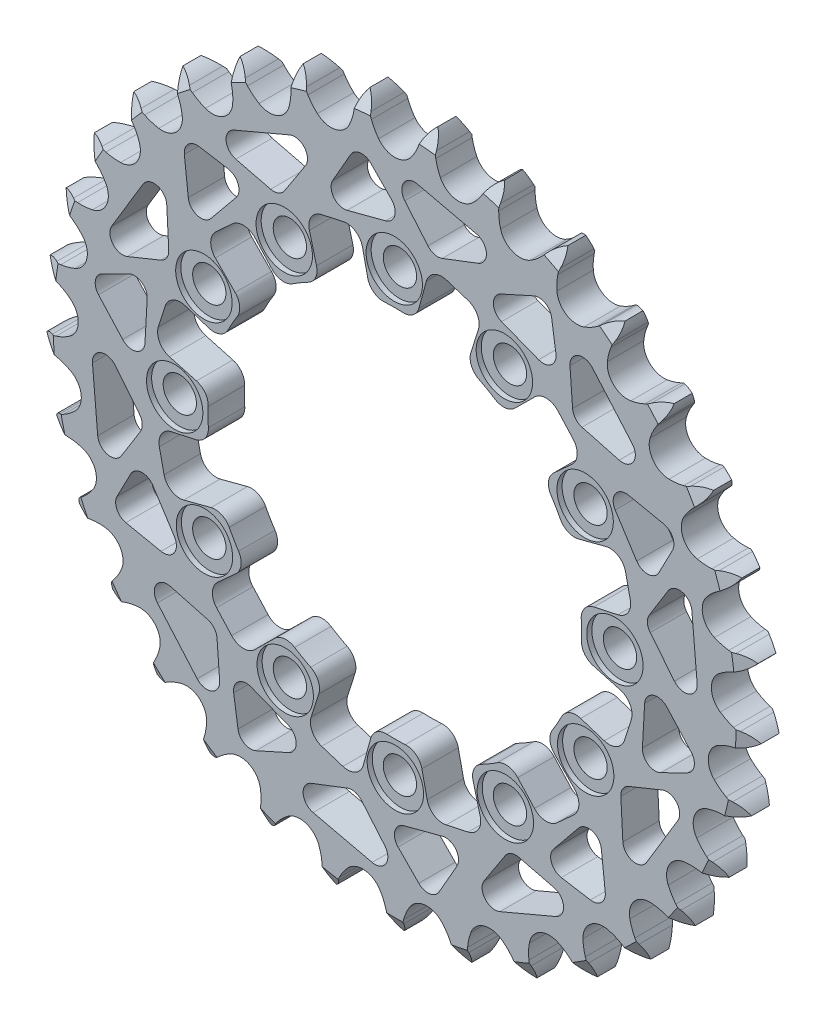
SolidWorks part; units mm, degrees
other "Markup1"
sketch "Sketch16" plane through (70.768, -70.8482, 7.2136) normal (0.1919, -0.04, 0.9806) x (0.9727, -0.1249, -0.1954)
sketch "Sketch17" plane through (70.768, -70.8482, 7.2136) normal (0.1919, -0.04, 0.9806) x (0.9727, -0.1249, -0.1954)
sketch "Sketch18" plane through (70.768, -70.8482, 7.2136) normal (0.1919, -0.04, 0.9806) x (0.9727, -0.1249, -0.1954)
sketch "Sketch19" plane through (70.768, -70.8482, 7.2136) normal (0.1919, -0.04, 0.9806) x (0.9727, -0.1249, -0.1954)
sketch "Sketch20" plane through (70.768, -70.8482, 7.2136) normal (0.1919, -0.04, 0.9806) x (0.9727, -0.1249, -0.1954)
sketch "Sketch24" plane through (70.768, -70.8482, 7.2136) normal (0.1919, -0.04, 0.9806) x (0.9727, -0.1249, -0.1954)
sketch "Sketch25" plane through (70.768, -70.8482, 7.2136) normal (0.1919, -0.04, 0.9806) x (0.9727, -0.1249, -0.1954)
sketch "Sketch26" plane through (70.768, -70.8482, 7.2136) normal (0.1919, -0.04, 0.9806) x (0.9727, -0.1249, -0.1954)
sketch "Sketch27" plane through (70.768, -70.8482, 7.2136) normal (0.1919, -0.04, 0.9806) x (0.9727, -0.1249, -0.1954)
sketch "Sketch28" plane through (70.768, -70.8482, 7.2136) normal (0.1919, -0.04, 0.9806) x (0.9727, -0.1249, -0.1954)
material "7075-T6 (SN)"
ref_plane "Front Plane" through (0, 0, 0) normal (0, 0, 1) x (1, 0, 0)
ref_plane "Top Plane" through (0, 0, 0) normal (0, 1, 0) x (1, 0, 0)
ref_plane "Right Plane" through (0, 0, 0) normal (1, 0, 0) x (0, 0, -1)
sketch "Work Sketch" plane through (0, 0, 0) normal (0, 0, 1) x (1, 0, 0)
  line L0 (0, 0) -> (0, 160.4542) construction
  line L1 (-112.0919, 66.8027) -> (87.2579, 66.8027) construction
  line L2 (5.0834, 120.8822) -> (5.0834, 112.9699) construction
  line L3 (-12.8497, 70.6081) -> (16.7256, 70.6081) construction
  line L4 (5.0834, 70.6081) -> (-6.0658, 62.2619) construction
  line L5 (5.0834, 70.6081) -> (-4.6352, 66.9715) construction
  line L6 (-4.6352, 66.9715) -> (-6.998, 73.2861)
  line L7 (-11.5114, 65.7464) -> (-7.1525, 65.7464) construction
  line L8 (-11.0622, 124.7602) -> (-11.0622, 110.2345) construction
  line L9 (0, 0) -> (-4.0639, 42.5596) construction
  circle A0 centre (0, 0) radius 66.8027
  circle A1 centre (0, 66.8027) radius 4.0088
  arc A2 (-4.6352, 66.9715) -> (-3.2092, 64.4003) centre (5.0609, 70.6677) ccw
  circle A3 centre (-11.0622, 65.7464) radius 6.4488
  point P23 (-3.2092, 64.4003)
  dimension "D1" = 133.6054
  dimension "D8" = 10.3767
  dimension "D2" = 8.0177
  dimension "D3" = 5.0834
  dimension "D4" = 3.8054
  dimension "D5" = 36.818
  dimension "D6" = 16.303
  dimension "D7" = 10.3767
  dimension "D9" = 1.0563
  dimension "D10" = 11.0622
  dimension "D11" = 5.455
sketch "Teeth Sketch" plane through (0, 0, 0) normal (0, 0, 1) x (1, 0, 0)
  line L0 (5.0224, 68.0064) -> (4.6352, 66.9715)
  line L1 (-8.8439, 92.6176) -> (-5.6513, 59.1829) construction
  line L2 (0, 0) -> (-12.8498, 132.1321) construction
  line L3 (7.9387, 67.7279) -> (8.123, 66.6385)
  line L4 (19011.2087, -199094.3845) -> (-19015.2726, 199136.9441) construction
  line L5 (0, 146.3285) -> (0, 56.9858) construction
  line L6 (17.8019, 65.8269) -> (17.2258, 64.8841)
  line L7 (0, -200000) -> (0, 200160.4542) construction
  line L8 (20.6128, 65.0016) -> (20.5877, 63.897)
  line L9 (-4.6352, 66.9715) -> (-6.998, 73.2861) construction
  line L10 (43.2949, 52.6844) -> (42.861, 51.6682)
  line L11 (-5.0224, 68.0064) -> (-4.6352, 66.9715)
  line L12 (29.938, 61.2683) -> (29.1939, 60.4515)
  line L13 (32.5419, 59.9259) -> (32.3082, 58.846)
  line L14 (40.9921, 54.4953) -> (40.1069, 53.8341)
  line L15 (50.5647, 45.7527) -> (49.5703, 45.271)
  line L16 (52.4831, 43.5387) -> (51.8648, 42.623)
  line L17 (58.3096, 35.3565) -> (57.2421, 35.0716)
  line L18 (59.7744, 32.8194) -> (58.9939, 32.0373)
  line L19 (63.9472, 23.6824) -> (62.845, 23.6047)
  line L20 (64.9053, 20.9139) -> (63.9909, 20.2936)
  line L21 (67.2735, 11.1523) -> (66.1765, 11.2846)
  line L22 (67.6904, 8.2526) -> (66.6751, 7.8165)
  line L23 (68.1683, -1.7808) -> (67.1162, -1.4433)
  line L24 (68.0289, -4.7071) -> (66.9495, -4.9431)
  line L25 (66.5994, -14.6496) -> (65.6302, -14.119)
  line L26 (65.9088, -17.4966) -> (64.8042, -17.524)
  line L27 (62.6234, -26.9889) -> (61.7722, -26.2845)
  line L28 (61.4065, -29.6537) -> (60.3166, -29.4716)
  line L29 (56.3841, -38.3527) -> (55.6815, -37.4999)
  line L30 (54.6848, -40.739) -> (53.6491, -40.354)
  line L31 (48.1068, -48.3304) -> (47.5783, -47.3601)
  line L32 (45.9866, -50.352) -> (45.0425, -49.7779)
  line L33 (38.0909, -56.5613) -> (37.7556, -55.5085)
  line L34 (35.6264, -58.1451) -> (34.808, -57.4027)
  line L35 (26.6983, -62.7479) -> (26.5682, -61.6506)
  line L36 (23.9786, -63.8367) -> (23.3155, -62.9529)
  line L37 (14.3407, -66.6666) -> (14.4207, -65.5646)
  line L38 (11.4641, -67.221) -> (10.9802, -66.2277)
  line L39 (1.4648, -68.1759) -> (1.7519, -67.1089)
  line L40 (-1.4648, -68.1759) -> (-1.7519, -67.1089)
  line L41 (-11.4641, -67.221) -> (-10.9802, -66.2277)
  line L42 (-14.3407, -66.6666) -> (-14.4207, -65.5646)
  line L43 (-23.9786, -63.8367) -> (-23.3155, -62.9529)
  line L44 (-26.6983, -62.7479) -> (-26.5682, -61.6506)
  line L45 (-35.6264, -58.1451) -> (-34.808, -57.4027)
  line L46 (-38.0909, -56.5613) -> (-37.7556, -55.5085)
  line L47 (-45.9866, -50.352) -> (-45.0425, -49.7779)
  line L48 (-48.1068, -48.3304) -> (-47.5783, -47.3601)
  line L49 (-54.6848, -40.739) -> (-53.6491, -40.354)
  line L50 (-56.3841, -38.3527) -> (-55.6815, -37.4999)
  line L51 (-61.4065, -29.6537) -> (-60.3166, -29.4716)
  line L52 (-62.6234, -26.9889) -> (-61.7722, -26.2845)
  line L53 (-65.9088, -17.4966) -> (-64.8042, -17.524)
  line L54 (-66.5994, -14.6496) -> (-65.6302, -14.119)
  line L55 (-68.0289, -4.7071) -> (-66.9495, -4.9431)
  line L56 (-68.1683, -1.7808) -> (-67.1162, -1.4433)
  line L57 (-67.6904, 8.2526) -> (-66.6751, 7.8165)
  line L58 (-67.2735, 11.1523) -> (-66.1765, 11.2846)
  line L59 (-64.9053, 20.9139) -> (-63.9909, 20.2936)
  line L60 (-63.9472, 23.6824) -> (-62.845, 23.6047)
  line L61 (-59.7744, 32.8194) -> (-58.9939, 32.0373)
  line L62 (-58.3096, 35.3565) -> (-57.2421, 35.0716)
  line L63 (-52.4831, 43.5387) -> (-51.8648, 42.623)
  line L64 (-50.5647, 45.7527) -> (-49.5703, 45.271)
  line L65 (-43.2949, 52.6844) -> (-42.861, 51.6682)
  line L66 (-40.9921, 54.4953) -> (-40.1069, 53.8341)
  line L67 (-32.5419, 59.9259) -> (-32.3082, 58.846)
  line L68 (-29.938, 61.2683) -> (-29.1939, 60.4515)
  line L69 (-20.6128, 65.0016) -> (-20.5877, 63.897)
  line L70 (-17.8019, 65.8269) -> (-17.2258, 64.8841)
  line L71 (-7.9387, 67.7279) -> (-8.123, 66.6385)
  arc A0 (-6.8704, 70.647) -> (-5.0224, 68.0064) centre (-11.0622, 65.7464) cw
  circle A1 centre (-11.0622, 65.7464) radius 6.4488 construction
  arc A2 (-3.2092, 64.4003) -> (-4.6352, 66.9715) centre (5.0609, 70.6677) cw
  arc A3 (-4.6352, 66.9715) -> (-3.2092, 64.4003) centre (5.0609, 70.6677) ccw construction
  circle A4 centre (0, 66.8027) radius 4.0088 construction
  arc A5 (-3.2092, 64.4003) -> (3.2092, 64.4003) centre (0, 66.8027) ccw
  arc A6 (3.2092, 64.4003) -> (4.6352, 66.9715) centre (-5.0609, 70.6677) ccw
  arc A7 (6.8704, 70.647) -> (5.0224, 68.0064) centre (11.0622, 65.7464) ccw
  arc A8 (6.6238, 70.6705) -> (7.9387, 67.7279) centre (1.5803, 66.6518) cw
  arc A9 (9.0366, 63.8438) -> (8.123, 66.6385) centre (18.3434, 68.4328) cw
  arc A10 (9.0366, 63.8438) -> (15.3391, 62.6291) centre (12.6425, 65.5955) ccw
  arc A11 (15.3391, 62.6291) -> (17.2258, 64.8841) centre (8.4044, 70.3484) ccw
  arc A12 (20.1163, 68.0701) -> (17.8019, 65.8269) centre (23.3049, 62.4647) ccw
  arc A13 (19.8786, 68.1399) -> (20.6128, 65.0016) centre (14.1657, 65.1482) cw
  arc A14 (20.9558, 60.9799) -> (20.5877, 63.897) centre (30.9629, 63.7246) cw
  arc A15 (20.9558, 60.9799) -> (26.9145, 58.5944) centre (24.8281, 62.0175) ccw
  arc A16 (26.9145, 58.5944) -> (29.1939, 60.4515) centre (21.5661, 67.4865) ccw
  arc A17 (32.6351, 63.0329) -> (29.938, 61.2683) centre (34.7052, 56.9254) ccw
  arc A18 (32.4149, 63.1465) -> (32.5419, 59.9259) centre (26.2391, 61.29) cw
  arc A19 (32.1176, 55.912) -> (32.3082, 58.846) centre (42.4634, 56.7133) cw
  arc A20 (32.1176, 55.912) -> (37.5172, 52.4419) centre (36.1163, 56.198) ccw
  arc A21 (37.5172, 52.4419) -> (40.1069, 53.8341) centre (33.9483, 62.1856) ccw
  arc A22 (43.9744, 55.7176) -> (40.9921, 54.4953) centre (44.8513, 49.3287) ccw
  arc A23 (43.7796, 55.8708) -> (43.2949, 52.6844) centre (37.3641, 55.2167) cw
  arc A24 (42.1187, 48.8233) -> (42.861, 51.6682) centre (52.429, 47.6521) cw
  arc A25 (42.1187, 48.8233) -> (46.7639, 44.3941) centre (46.0991, 48.3474) ccw
  arc A26 (46.7639, 44.3941) -> (49.5703, 45.271) centre (45.1035, 54.637) ccw
  arc A27 (53.7244, 46.3885) -> (50.5647, 45.7527) centre (53.3763, 39.9491) ccw
  arc A28 (53.5621, 46.5757) -> (52.4831, 43.5387) centre (47.1387, 47.1476) cw
  arc A29 (50.5974, 39.97) -> (51.8648, 42.623) centre (60.4998, 36.8687) cw
  arc A30 (50.5974, 39.97) -> (54.3205, 34.7417) centre (54.4159, 38.7494) ccw
  arc A31 (54.3205, 34.7417) -> (57.2421, 35.0716) centre (54.6285, 45.1138) ccw
  arc A32 (61.5326, 35.3828) -> (58.3096, 35.3565) centre (59.9721, 29.1257) ccw
  arc A33 (61.4087, 35.5974) -> (59.7744, 32.8194) centre (55.2096, 37.3746) cw
  arc A34 (57.2474, 29.6721) -> (58.9939, 32.0373) centre (66.384, 24.7528) cw
  arc A35 (57.2474, 29.6721) -> (59.9137, 23.8336) centre (60.7659, 27.7508) ccw
  arc A36 (59.9137, 23.8336) -> (62.845, 23.6047) centre (62.1792, 33.96) ccw
  arc A37 (67.1168, 23.0983) -> (63.9472, 23.6824) centre (64.4004, 17.2495) ccw
  arc A38 (67.0358, 23.3324) -> (64.9053, 20.9139) centre (61.2851, 26.2507) cw
  arc A39 (61.8283, 18.3017) -> (63.9909, 20.2936) centre (69.8688, 11.7422) cw
  arc A40 (61.8283, 18.3017) -> (63.3416, 12.0642) centre (64.9196, 15.7493) ccw
  arc A41 (63.3416, 12.0642) -> (66.1765, 11.2846) centre (67.4825, 21.5788) ccw
  arc A42 (70.2753, 9.9789) -> (67.2735, 11.1523) centre (66.5011, 4.7499) ccw
  arc A43 (70.2401, 10.2242) -> (67.6904, 8.2526) centre (65.1456, 14.178) cw
  arc A44 (64.1746, 6.2699) -> (66.6751, 7.8165) centre (70.8284, -1.6927) cw
  arc A45 (64.1746, 6.2699) -> (64.48, -0.1413) centre (66.727, 3.1786) ccw
  arc A46 (64.48, -0.1413) -> (67.1162, -1.4433) centre (70.3468, 8.4177) ccw
  arc A47 (70.8939, -3.5011) -> (68.1683, -1.7808) centre (66.1983, -7.9213) ccw
  arc A48 (70.9057, -3.2536) -> (68.0289, -4.7071) centre (66.6515, 1.5929) cw
  arc A49 (64.2015, -5.9885) -> (66.9495, -4.9431) centre (69.2281, -15.0665) cw
  arc A50 (64.2015, -5.9885) -> (63.2881, -12.3417) centre (66.1227, -9.507) ccw
  arc A51 (63.2881, -12.3417) -> (65.6302, -14.119) centre (70.6686, -5.0476) ccw
  arc A52 (68.9501, -16.8546) -> (66.5994, -14.6496) centre (63.5029, -20.3063) ccw
  arc A53 (69.0085, -16.6138) -> (65.9088, -17.4966) centre (65.7485, -11.0498) cw
  arc A54 (61.908, -18.0305) -> (64.8042, -17.524) centre (65.1257, -27.8957) cw
  arc A55 (61.908, -18.0305) -> (59.8087, -24.096) centre (63.1286, -21.849) ccw
  arc A56 (59.8087, -24.096) -> (61.7722, -26.2845) centre (68.4363, -18.3305) ccw
  arc A57 (64.5144, -29.5989) -> (62.6234, -26.9889) centre (58.5123, -31.9573) ccw
  arc A58 (64.6173, -29.3735) -> (61.4065, -29.6537) centre (62.4691, -23.2931) cw
  arc A59 (57.3769, -29.4209) -> (60.3166, -29.4716) centre (58.6695, -39.7167) cw
  arc A60 (57.3769, -29.4209) -> (54.1677, -34.9794) centre (57.8528, -33.4013) ccw
  arc A61 (54.1677, -34.9794) -> (55.6815, -37.4999) centre (63.7305, -30.9509) ccw
  arc A62 (57.7469, -41.2734) -> (56.3841, -38.3527) centre (51.4069, -42.4533) ccw
  arc A63 (57.8906, -41.0716) -> (54.6848, -40.739) centre (56.932, -34.6945) cw
  arc A64 (50.7721, -39.7478) -> (53.6491, -40.354) centre (50.0928, -50.1023) cw
  arc A65 (50.7721, -39.7478) -> (46.5689, -44.5986) centre (50.4861, -43.7465) ccw
  arc A66 (46.5689, -44.5986) -> (47.5783, -47.3601) centre (56.7213, -42.4527) ccw
  arc A67 (48.8923, -51.4562) -> (48.1068, -48.3304) centre (42.4436, -51.415) ccw
  arc A68 (49.0716, -51.2853) -> (45.9866, -50.352) centre (49.3372, -44.842) cw
  arc A69 (42.3322, -48.6382) -> (45.0425, -49.7779) centre (39.7057, -58.677) cw
  arc A70 (42.3322, -48.6382) -> (37.287, -52.6059) centre (41.2947, -52.5105) ccw
  arc A71 (37.287, -52.6059) -> (37.7556, -55.5085) centre (47.662, -52.4201) ccw
  arc A72 (38.2706, -59.7793) -> (38.0909, -56.5613) centre (31.9463, -58.5183) ccw
  arc A73 (38.479, -59.6453) -> (35.6264, -58.1451) centre (39.9592, -53.3687) cw
  arc A74 (32.3624, -55.7707) -> (34.808, -57.4027) centre (27.8834, -65.131) cw
  arc A75 (32.3624, -55.7707) -> (26.6574, -58.7118) centre (30.6108, -59.3766) ccw
  arc A76 (26.6574, -58.7118) -> (26.5682, -61.6506) centre (36.8801, -60.4929) ccw
  arc A77 (26.2657, -65.9417) -> (26.6983, -62.7479) centre (20.2943, -63.5067) ccw
  arc A78 (26.4957, -65.8497) -> (23.9786, -63.8367) centre (29.137, -59.9666) cw
  arc A79 (21.2229, -60.8875) -> (23.3155, -62.9529) centre (15.0534, -69.2309) cw
  arc A80 (21.2229, -60.8875) -> (15.0644, -62.6958) centre (18.8205, -64.0967) ccw
  arc A81 (15.0644, -62.6958) -> (14.4207, -65.5646) centre (24.7653, -66.3793) ccw
  arc A82 (13.3114, -69.7209) -> (14.3407, -66.6666) centre (7.9088, -66.1998) ccw
  arc A83 (13.5547, -69.674) -> (11.4641, -67.221) centre (17.2617, -64.3972) cw
  arc A84 (9.3163, -63.8036) -> (10.9802, -66.2277) centre (1.6794, -70.8287) cw
  arc A85 (9.3163, -63.8036) -> (2.9269, -64.4137) centre (6.35, -66.5002) ccw
  arc A86 (2.9269, -64.4137) -> (1.7519, -67.1089) centre (11.7554, -69.8666) ccw
  arc A87 (-0.1239, -70.9802) -> (1.4648, -68.1759) centre (-4.7625, -66.5002) ccw
  arc A88 (0.1239, -70.9802) -> (-1.4648, -68.1759) centre (4.7625, -66.5002) cw
  arc A89 (-2.9269, -64.4137) -> (-1.7519, -67.1089) centre (-11.7554, -69.8666) cw
  arc A90 (-2.9269, -64.4137) -> (-9.3163, -63.8036) centre (-6.35, -66.5002) ccw
  arc A91 (-9.3163, -63.8036) -> (-10.9802, -66.2277) centre (-1.6794, -70.8287) ccw
  arc A92 (-13.5547, -69.674) -> (-11.4641, -67.221) centre (-17.2617, -64.3972) ccw
  arc A93 (-13.3114, -69.7209) -> (-14.3407, -66.6666) centre (-7.9088, -66.1998) cw
  arc A94 (-15.0644, -62.6958) -> (-14.4207, -65.5646) centre (-24.7653, -66.3793) cw
  arc A95 (-15.0644, -62.6958) -> (-21.2229, -60.8875) centre (-18.8205, -64.0967) ccw
  arc A96 (-21.2229, -60.8875) -> (-23.3155, -62.9529) centre (-15.0534, -69.2309) ccw
  arc A97 (-26.4957, -65.8497) -> (-23.9786, -63.8367) centre (-29.137, -59.9666) ccw
  arc A98 (-26.2657, -65.9417) -> (-26.6983, -62.7479) centre (-20.2943, -63.5067) cw
  arc A99 (-26.6574, -58.7118) -> (-26.5682, -61.6506) centre (-36.8801, -60.4929) cw
  arc A100 (-26.6574, -58.7118) -> (-32.3624, -55.7707) centre (-30.6108, -59.3766) ccw
  arc A101 (-32.3624, -55.7707) -> (-34.808, -57.4027) centre (-27.8834, -65.131) ccw
  arc A102 (-38.479, -59.6453) -> (-35.6264, -58.1451) centre (-39.9592, -53.3687) ccw
  arc A103 (-38.2706, -59.7793) -> (-38.0909, -56.5613) centre (-31.9463, -58.5183) cw
  arc A104 (-37.287, -52.6059) -> (-37.7556, -55.5085) centre (-47.662, -52.4201) cw
  arc A105 (-37.287, -52.6059) -> (-42.3322, -48.6382) centre (-41.2947, -52.5105) ccw
  arc A106 (-42.3322, -48.6382) -> (-45.0425, -49.7779) centre (-39.7057, -58.677) ccw
  arc A107 (-49.0716, -51.2853) -> (-45.9866, -50.352) centre (-49.3372, -44.842) ccw
  arc A108 (-48.8923, -51.4562) -> (-48.1068, -48.3304) centre (-42.4436, -51.415) cw
  arc A109 (-46.5689, -44.5986) -> (-47.5783, -47.3601) centre (-56.7213, -42.4527) cw
  arc A110 (-46.5689, -44.5986) -> (-50.7721, -39.7478) centre (-50.4861, -43.7465) ccw
  arc A111 (-50.7721, -39.7478) -> (-53.6491, -40.354) centre (-50.0928, -50.1023) ccw
  arc A112 (-57.8906, -41.0716) -> (-54.6848, -40.739) centre (-56.932, -34.6945) ccw
  arc A113 (-57.7469, -41.2734) -> (-56.3841, -38.3527) centre (-51.4069, -42.4533) cw
  arc A114 (-54.1677, -34.9794) -> (-55.6815, -37.4999) centre (-63.7305, -30.9509) cw
  arc A115 (-54.1677, -34.9794) -> (-57.3769, -29.4209) centre (-57.8528, -33.4013) ccw
  arc A116 (-57.3769, -29.4209) -> (-60.3166, -29.4716) centre (-58.6695, -39.7167) ccw
  arc A117 (-64.6173, -29.3735) -> (-61.4065, -29.6537) centre (-62.4691, -23.2931) ccw
  arc A118 (-64.5144, -29.5989) -> (-62.6234, -26.9889) centre (-58.5123, -31.9573) cw
  arc A119 (-59.8087, -24.096) -> (-61.7722, -26.2845) centre (-68.4363, -18.3305) cw
  arc A120 (-59.8087, -24.096) -> (-61.908, -18.0305) centre (-63.1286, -21.849) ccw
  arc A121 (-61.908, -18.0305) -> (-64.8042, -17.524) centre (-65.1257, -27.8957) ccw
  arc A122 (-69.0085, -16.6138) -> (-65.9088, -17.4966) centre (-65.7485, -11.0498) ccw
  arc A123 (-68.9501, -16.8546) -> (-66.5994, -14.6496) centre (-63.5029, -20.3063) cw
  arc A124 (-63.2881, -12.3417) -> (-65.6302, -14.119) centre (-70.6686, -5.0476) cw
  arc A125 (-63.2881, -12.3417) -> (-64.2015, -5.9885) centre (-66.1227, -9.507) ccw
  arc A126 (-64.2015, -5.9885) -> (-66.9495, -4.9431) centre (-69.2281, -15.0665) ccw
  arc A127 (-70.9057, -3.2536) -> (-68.0289, -4.7071) centre (-66.6515, 1.5929) ccw
  arc A128 (-70.8939, -3.5011) -> (-68.1683, -1.7808) centre (-66.1983, -7.9213) cw
  arc A129 (-64.48, -0.1413) -> (-67.1162, -1.4433) centre (-70.3468, 8.4177) cw
  arc A130 (-64.48, -0.1413) -> (-64.1746, 6.2699) centre (-66.727, 3.1786) ccw
  arc A131 (-64.1746, 6.2699) -> (-66.6751, 7.8165) centre (-70.8284, -1.6927) ccw
  arc A132 (-70.2401, 10.2242) -> (-67.6904, 8.2526) centre (-65.1456, 14.178) ccw
  arc A133 (-70.2753, 9.9789) -> (-67.2735, 11.1523) centre (-66.5011, 4.7499) cw
  arc A134 (-63.3416, 12.0642) -> (-66.1765, 11.2846) centre (-67.4825, 21.5788) cw
  arc A135 (-63.3416, 12.0642) -> (-61.8283, 18.3017) centre (-64.9196, 15.7493) ccw
  arc A136 (-61.8283, 18.3017) -> (-63.9909, 20.2936) centre (-69.8688, 11.7422) ccw
  arc A137 (-67.0358, 23.3324) -> (-64.9053, 20.9139) centre (-61.2851, 26.2507) ccw
  arc A138 (-67.1168, 23.0983) -> (-63.9472, 23.6824) centre (-64.4004, 17.2495) cw
  arc A139 (-59.9137, 23.8336) -> (-62.845, 23.6047) centre (-62.1792, 33.96) cw
  arc A140 (-59.9137, 23.8336) -> (-57.2474, 29.6721) centre (-60.7659, 27.7508) ccw
  arc A141 (-57.2474, 29.6721) -> (-58.9939, 32.0373) centre (-66.384, 24.7528) ccw
  arc A142 (-61.4087, 35.5974) -> (-59.7744, 32.8194) centre (-55.2096, 37.3746) ccw
  arc A143 (-61.5326, 35.3828) -> (-58.3096, 35.3565) centre (-59.9721, 29.1257) cw
  arc A144 (-54.3205, 34.7417) -> (-57.2421, 35.0716) centre (-54.6285, 45.1138) cw
  arc A145 (-54.3205, 34.7417) -> (-50.5974, 39.97) centre (-54.4159, 38.7494) ccw
  arc A146 (-50.5974, 39.97) -> (-51.8648, 42.623) centre (-60.4998, 36.8687) ccw
  arc A147 (-53.5621, 46.5757) -> (-52.4831, 43.5387) centre (-47.1387, 47.1476) ccw
  arc A148 (-53.7244, 46.3885) -> (-50.5647, 45.7527) centre (-53.3763, 39.9491) cw
  arc A149 (-46.7639, 44.3941) -> (-49.5703, 45.271) centre (-45.1035, 54.637) cw
  arc A150 (-46.7639, 44.3941) -> (-42.1187, 48.8233) centre (-46.0991, 48.3474) ccw
  arc A151 (-42.1187, 48.8233) -> (-42.861, 51.6682) centre (-52.429, 47.6521) ccw
  arc A152 (-43.7796, 55.8708) -> (-43.2949, 52.6844) centre (-37.3641, 55.2167) ccw
  arc A153 (-43.9744, 55.7176) -> (-40.9921, 54.4953) centre (-44.8513, 49.3287) cw
  arc A154 (-37.5172, 52.4419) -> (-40.1069, 53.8341) centre (-33.9483, 62.1856) cw
  arc A155 (-37.5172, 52.4419) -> (-32.1176, 55.912) centre (-36.1163, 56.198) ccw
  arc A156 (-32.1176, 55.912) -> (-32.3082, 58.846) centre (-42.4634, 56.7133) ccw
  arc A157 (-32.4149, 63.1465) -> (-32.5419, 59.9259) centre (-26.2391, 61.29) ccw
  arc A158 (-32.6351, 63.0329) -> (-29.938, 61.2683) centre (-34.7052, 56.9254) cw
  arc A159 (-26.9145, 58.5944) -> (-29.1939, 60.4515) centre (-21.5661, 67.4865) cw
  arc A160 (-26.9145, 58.5944) -> (-20.9558, 60.9799) centre (-24.8281, 62.0175) ccw
  arc A161 (-20.9558, 60.9799) -> (-20.5877, 63.897) centre (-30.9629, 63.7246) ccw
  arc A162 (-19.8786, 68.1399) -> (-20.6128, 65.0016) centre (-14.1657, 65.1482) ccw
  arc A163 (-20.1163, 68.0701) -> (-17.8019, 65.8269) centre (-23.3049, 62.4647) cw
  arc A164 (-15.3391, 62.6291) -> (-17.2258, 64.8841) centre (-8.4044, 70.3484) cw
  arc A165 (-15.3391, 62.6291) -> (-9.0366, 63.8438) centre (-12.6425, 65.5955) ccw
  arc A166 (-9.0366, 63.8438) -> (-8.123, 66.6385) centre (-18.3434, 68.4328) ccw
  arc A167 (-6.6238, 70.6705) -> (-7.9387, 67.7279) centre (-1.5803, 66.6518) ccw
  point P77 (0, 0)
  dimension "D1" = 5.455
  dimension "D2" = 5.555
  dimension "D3" = 33
extrude "Extrusion" add sketch "Teeth Sketch" along normal blind 7.2136
hole_wizard "M6 Clearance Hole1" positions "Sketch6" profile "Sketch7" hole size "M6" standard "ANSI Metric"
sketch "Sketch6" plane through (0, 0, 0) normal (0, 0, -1) x (-1, 0, 0)
  circle A0 centre (0, 0) radius 43.5
  point P0 (0, 43.5)
  dimension "D1" = 87
sketch "Sketch7" plane through (0, 43.5, 0) normal (1, 0, 0) x (0, 1, 0)
  line L0 (0, 0) -> (0, 19.2548)
  line L1 (0, 19.2548) -> (3.3, 17.272)
  line L2 (3.3, 17.272) -> (3.3, 0)
  line L5 (3.3, 0) -> (0, 0)
  line L10 (0, 19.2548) -> (-3.3, 17.272) construction
  line L11 (0, -6.35) -> (0, 107.95) construction
  dimension "Hole Dia." = 6.6
  dimension "Hole Depth" = 17.272
  dimension "Drill Angle" = 118
pattern_circular "CirPattern1" count 12 over 360 about axis through (0, -0.1107, 0) along (0, 0, 1) of "M6 Clearance Hole1"
sketch "Sketch8" plane through (0, 0, 0) normal (0, 0, -1) x (-1, 0, 0)
  circle A0 centre (0, 0) radius 37
  dimension "D1" = 74
extrude "Cut-Extrude1" cut sketch "Sketch8" against normal through all both and the other way through all
ref_plane "Sprocket Center Plane" through (0, 0, 3.6068) normal (0, 0, 1) x (1, 0, 0)
sketch "Pitch Circle" plane through (0, 0, 3.6068) normal (0, 0, -1) x (-1, 0, 0)
  circle A0 centre (0, 0) radius 66.8027 construction
  dimension "D1" = 133.6054
ref_plane "Center Plane" through (0, 0, 3.6068) normal (0, 0, 1) x (1, 0, 0)
ref_axis "Axis1" through (0, 0, 7.2136) along (0, 0, -1)
sketch "Sketch5" plane through (0, 0, 0) normal (1, 0, 0) x (0, 0, -1)
  line L0 (-1.8288, -70.8482) -> (-5.3848, -70.8482)
  line L1 (-7.2136, -51.2753) -> (0, -51.2753) construction
  line L2 (-5.3848, -70.8482) -> (-5.3848, -67.6547)
  line L3 (-5.3848, -67.6547) -> (-7.2136, -67.6547)
  line L4 (-7.2136, -67.6547) -> (-5.3848, -70.8482)
  line L5 (-7.2136, -67.6547) -> (-7.2136, -70.8482)
  line L6 (-7.2136, -70.8482) -> (-5.3848, -70.8482)
  line L8 (-7.2136, -70.8482) -> (0, -70.8482) construction
  line L9 (-7.2136, -68.1759) -> (-7.2136, -70.8482) construction
  dimension "D1" = 3.556
  dimension "D2" = 3.1936
  dimension "D3" = 1.8288
revolve "Cut-Revolve1" cut sketch "Sketch5" angle 360 about axis through (0, 0, 7.2136) along (0, 0, -1)
mirror "Mirror1" about plane through (0, 0, 3.6068) normal (0, 0, 1) of "Cut-Revolve1"
sketch "Sketch10" plane through (0, 0, 0) normal (0, 0, 1) x (1, 0, 0)
  line L0 (0, 0) -> (-79.643, -0.2022) construction
  line L1 (0, 0) -> (-79.6429, 10.0842) construction
  line L2 (0, 0) -> (-79.643, -10.4954) construction
  line L3 (-59.2423, 9.0305) -> (-51.4071, 1.075)
  line L5 (-49.1987, 6.2294) -> (-49.1987, 5.0699)
  line L6 (-51.4071, 1.075) -> (-62.5732, 1.075)
  line L8 (-62.7341, -1.6349) -> (-51.5692, -1.4798)
  line L9 (-51.5692, -1.4798) -> (-59.2931, -9.5434)
  line L12 (-49.1987, -0.1249) -> (-49.1987, -0.1107)
  line L15 (-51.5692, -1.4798) -> (-53.764, -1.4798) construction
  line L16 (-51.4071, 1.075) -> (-52.3044, 1.075) construction
  line L17 (-59.2423, 9.0305) -> (-62.5732, 1.075)
  line L18 (-62.7341, -1.6349) -> (-59.2931, -9.5434)
  line L19 (-45.388, 21.6946) -> (-49.1987, 5.0699)
  line L20 (-31.807, 16.9479) -> (-36.0091, 0.4177)
  line L22 (-49.1987, -0.1107) -> (-49.1987, -0.1249)
  line L23 (-49.1987, 5.0699) -> (-49.1987, 6.2294)
  circle A0 centre (-43.6107, -0.1107) radius 5.588
  circle A1 centre (-37.768, 21.6946) radius 5.588
  arc A2 (-36.0091, 0.4177) -> (-49.1987, 5.0699) centre (-43.6107, -0.1107) ccw
  arc A3 (-45.388, 21.6946) -> (-31.807, 16.9479) centre (-37.768, 21.6946) ccw
  dimension "D1" = 11.176
  dimension "D12" = 15.24
  dimension "D2" = 4.8001
  dimension "D3" = 0.7635
  dimension "D4" = 35.8718
  dimension "D6" = 11.165
  dimension "D8" = 2.7099
  dimension "D10" = 11.166
  dimension "D11" = 7.9555
  dimension "D13" = 35.0021
extrude "Cut-Extrude2" cut sketch "Sketch10" against normal blind 1.016 from surface at 7.2136 contours A0 starting at face at (-37, 0, 7.2136)
pattern_circular "CirPattern2" count 12 over 360 about axis through (0, 0, 0) along (0, 0, 1) of "Cut-Extrude2"
ref_plane "Half Plane" through (0, 0, 3.6068) normal (0, 0, 1) x (1, 0, 0)
sketch "Motor Shaft Sprocket Dimensions" plane through (0, 0, 3.6068) normal (0, 0, 1) x (1, 0, 0)
  line L0 (0, 0) -> (-177.8, 0)
  line L1 (-177.8, 0) -> (-177.8, 23.6982)
  line L2 (-180.2273, 51.0991) -> (-5.8945, 66.5421)
  line L3 (-187.3193, -2.1104) -> (-23.1174, -62.6753)
  line L4 (-5.8945, 66.5421) -> (0, 0)
  line L5 (0, 0) -> (-23.1174, -62.6753)
  circle A0 centre (-177.8, 23.6982) radius 27.5082
  circle A1 centre (0, 0) radius 66.8027 construction
  dimension "D3" = 55.0164
  dimension "D1" = 177.8
  dimension "D2" = 23.6982
  dimension "D4" = 205.308
sketch "Sketch12" plane through (0, 0, 7.2136) normal (0, 0, 1) x (1, 0, 0)
  line L4 (6.2506, 44.6668) -> (4.4901, 38.2464)
  line L5 (6.7125, 34.3449) -> (10.7295, 33.2434)
  line L10 (14.5937, 35.3397) -> (16.5644, 41.5116)
  line L11 (14.5056, 45.5019) -> (10.2783, 46.8517)
  arc A1 (4.4901, 38.2464) -> (6.7125, 34.3449) centre (7.5521, 37.4069) ccw
  arc A2 (10.7295, 33.2434) -> (14.5937, 35.3397) centre (11.5691, 36.3054) ccw
  arc A3 (16.5644, 41.5116) -> (14.5056, 45.5019) centre (13.5398, 42.4774) ccw
  arc A4 (10.2783, 46.8517) -> (6.2506, 44.6668) centre (9.3125, 43.8272) ccw
  point P8 (13.6671, 32.4379)
  point P11 (17.5302, 44.5362)
  point P14 (7.1257, 47.8584)
  dimension "D3" = 3.175
  dimension "D7" = 37.4069
  dimension "D1" = 10.922
  dimension "D2" = 12.7
  dimension "D4" = 34.8973
  dimension "D5" = 3.1527
  dimension "D6" = 47.7581
extrude "Cut-Extrude5" cut sketch "Sketch12" against normal up to next
pattern_circular "CirPattern3" count 12 over 360 about axis through (0, 0, 0) along (0, 0, 1) of "Cut-Extrude5"
sketch "Sketch13" plane through (0, 0, 7.2136) normal (0, 0, 1) x (1, 0, 0)
  line L6 (-12.295, 52.6993) -> (-8.767, 58.8746)
  line L7 (-4.7487, 59.3936) -> (-0.6568, 55.2241)
  line L8 (-1.8231, 50.9886) -> (-9.4431, 48.983)
  line L10 (1.9797, 56.3209) -> (6.5673, 50.8863)
  line L11 (9.4175, 50.1531) -> (16.5325, 52.881)
  line L12 (16.1956, 57.7273) -> (4.493, 60.434)
  arc A0 (-4.7487, 59.3936) -> (-8.767, 58.8746) centre (-6.5615, 57.6145) ccw
  arc A1 (-9.4431, 48.983) -> (-12.295, 52.6993) centre (-10.0896, 51.4393) cw
  arc A2 (-1.8231, 50.9886) -> (-0.6568, 55.2241) centre (-2.4696, 53.445) ccw
  arc A3 (9.4175, 50.1531) -> (6.5673, 50.8863) centre (8.5082, 52.5247) cw
  arc A4 (4.493, 60.434) -> (1.9797, 56.3209) centre (3.9206, 57.9593) ccw
  arc A5 (16.5325, 52.881) -> (16.1956, 57.7273) centre (15.6232, 55.2526) ccw
  arc A8 (9.0366, 63.8438) -> (15.3391, 62.6291) centre (12.6425, 65.5955) ccw construction
  point P22 (11.8838, 61.6591)
  dimension "D2" = 2.54
  dimension "D5" = 2.54
  dimension "D6" = 49.7732
  dimension "D1" = 2.54
  dimension "D3" = 2.54
  dimension "D4" = 2.54
  dimension "D14" = 38.2119
  dimension "D7" = 43.4577
  dimension "D8" = 59.8921
  dimension "D9" = 7.112
  dimension "D10" = 5.842
  dimension "D11" = 7.62
  dimension "D12" = 7.62
  dimension "D13" = 37.8425
  dimension "D15" = 2.8591
  dimension "D16" = 36.8183
  dimension ".28" = 7.112
extrude "Cut-Extrude7" cut sketch "Sketch13" against normal up to next
pattern_circular "CirPattern4" count 10 over 360 about axis through (0, 0, 0) along (0, 0, 1) of "Cut-Extrude7"
fillet "Fillet1" radius 3.175 24 edges at (5.0095, -36.6593, 3.6068) (-4.4498, -36.7315, 3.6068) (22.668, -29.2431, 3.6068) (14.5121, -34.0353, 3.6068) (29.5855, -22.2193, 3.6068) (34.2527, -13.9913, 3.6068) (36.7315, -4.4498, 3.6068) (36.6593, 5.0095, 3.6068) (29.2431, 22.668, 3.6068) (34.0353, 14.5121, 3.6068) (-13.9913, -34.2527, 3.6068) (-22.2193, -29.5855, 3.6068) (-29.2431, -22.668, 3.6068) (-34.0353, -14.5121, 3.6068) (-36.6593, -5.0095, 3.6068) (-36.7315, 4.4498, 3.6068) (-34.2527, 13.9913, 3.6068) (-29.5855, 22.2193, 3.6068) (-22.668, 29.2431, 3.6068) (-5.0095, 36.6593, 3.6068) (-14.5121, 34.0353, 3.6068) (4.4498, 36.7315, 3.6068) (13.9913, 34.2527, 3.6068) (22.2193, 29.5855, 3.6068)
equation "\"P\"= 0.500'//Chain Pitch"
equation "\"N\"= 33'//Number of Teeth"
equation "\"Dr\"= 5 / 16'//Roller Diameter"
equation "\"Ds\"= 1.0005 * \"Dr\" + 0.003'Seating Curve DIameter"
equation "\"R\"= \"Ds\" / 2"
equation "\"A\"= 35 + 60 / \"N\""
equation "\"B\"= 18 - 56 / \"N\""
equation "\"ac\"= 0.8 * \"Dr\""
equation "\"M\"= 0.8 * \"Dr\" * cos ( 35 + 60 / \"N\" )"
equation "\"T\"= 0.8 * \"Dr\" * sin ( 35 + 60 / \"N\" )"
equation "\"E\"= 1.3025 * \"Dr\" + 0.0015"
equation "\"Chordal Length of Arc xy\"= ( 2.605 * \"Dr\" + 0.003 ) * sin ( 9 - 28 / \"N\" )"
equation "\"yz\"= \"Dr\" * ( 1.4 * sin ( 17 - 64 / \"N\" ) - 0.8 * sin ( 18 - 56 / \"N\" ) )"
equation "\"ab\"= 1.4 * \"Dr\""
equation "\"W\"= 1.4 * \"Dr\" * cos ( 180 / \"N\" )"
equation "\"V\"= 1.4 * \"Dr\" * sin ( 180 / \"N\" )"
equation "\"F\"= \"Dr\" * ( 0.8 * cos ( 18 - 56 / \"N\" ) + 1.4 * cos ( 17 - 64 / \"N\" ) - 1.3025 )"
equation "\"H\"= sqr ( \"F\" ^ 2 - ( 1.4 * \"Dr\" - \"P\" / 2 ) ^ 2 )"
equation "\"S\"= \"P\" / 2 * cos ( 180 / \"N\" ) + \"H\" * sin ( 180 / \"N\" )"
equation "\"PD\"= \"P\" / ( sin ( 180 / \"N\" ) )"
equation "\"D1@Work Sketch\" = \"PD\""
equation "\"D3@Work Sketch\" = \"M\""
equation "\"D4@Work Sketch\" = \"T\""
equation "\"D5@Work Sketch\" = \"A\""
equation "\"D6@Work Sketch\" = \"B\""
equation "\"D7@Work Sketch\" = \"E\""
equation "\"D8@Work Sketch\" = \"E\""
equation "\"D9@Work Sketch\" = \"V\""
equation "\"D10@Work Sketch\" = \"W\""
equation "\"D2@Work Sketch\" = \"R\" * 2"
equation "\"D11@Work Sketch\" = 180 / \"N\""
equation "\"D2@Teeth Sketch\" = 180 / \"N\" + 0.1"
equation "\"D3@Teeth Sketch\" = \"N\""
equation "\"Edge Thickness\"=0.5"
equation "\"D1@Pitch Circle\"=\"PD\""
equation "\"ST\"= 0.284'//Sprocket Thickness"
